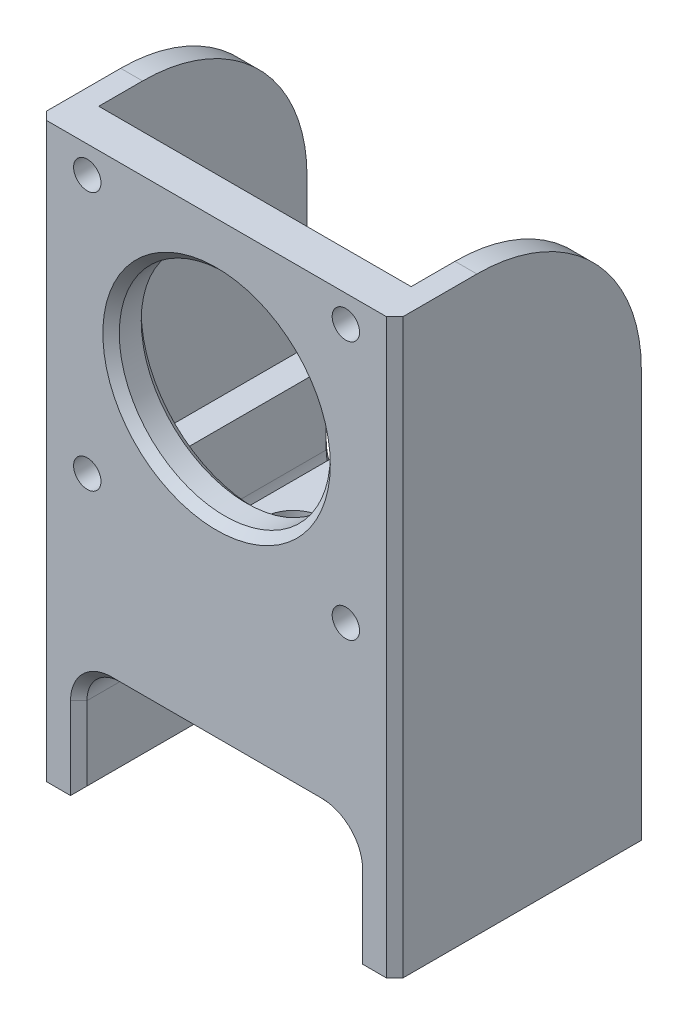
SolidWorks part; units mm, degrees
material "PET"
ref_plane "Front Plane" through (0, 0, 0) normal (0, 0, 1) x (1, 0, 0)
ref_plane "Top Plane" through (0, 0, 0) normal (0, 1, 0) x (1, 0, 0)
ref_plane "Right Plane" through (0, 0, 0) normal (1, 0, 0) x (0, 0, -1)
sketch "Sketch1" plane through (0, 0, 0) normal (0, 0, 1) x (1, 0, 0)
  line L0 (32.5, 28.5) -> (-32.5, 28.5)
  line L1 (-32.5, 28.5) -> (-32.5, -76)
  line L2 (-32.5, -76) -> (-25.15, -76)
  line L3 (-25.15, -76) -> (-25.15, -55)
  line L4 (-25.15, -55) -> (25.15, -55)
  line L5 (0, 28.5) -> (0, -55) construction
  line L6 (-33.5668, 0) -> (21.693, 0) construction
  line L7 (32.5, -76) -> (25.15, -76)
  line L8 (25.15, -76) -> (25.15, -55)
  line L9 (32.5, 28.5) -> (32.5, -76)
  circle A0 centre (0, 0) radius 19.25
  dimension "D1" = 38.5
  dimension "D2" = 65
  dimension "D3" = 28.5
  dimension "D4" = 76
  dimension "D5" = 50.3
  dimension "D6" = 55
extrude "Boss-Extrude1" add sketch "Sketch1" along normal mid plane 45
sketch "Sketch2" plane through (0, 0, -22.5) normal (0, 0, -1) x (-1, 0, 0)
  line L0 (-8.62, -49) -> (-23.5, -49)
  line L1 (-23.5, -28.5) -> (-8.62, -28.5) construction
  line L2 (-32.5, 28.5) -> (32.5, 28.5) construction
  line L3 (28.5, 28.5) -> (-28.5, 28.5)
  line L4 (-28.5, -28.5) -> (-28.5, 28.5)
  line L6 (25.15, -55) -> (-25.15, -55) construction
  line L7 (0, 64.9448) -> (0, 15.4596) construction
  line L8 (-8.62, -49) -> (-8.62, -28.5)
  line L9 (-8.62, -28.5) -> (8.62, -28.5)
  line L10 (-47.1134, 0) -> (-15.0079, 0) construction
  line L11 (8.62, -49) -> (23.5, -49)
  line L12 (8.62, -49) -> (8.62, -28.5)
  line L13 (-28.5, -28.5) -> (-23.5, -28.5)
  line L14 (-23.5, -49) -> (-23.5, -28.5)
  line L15 (23.5, -49) -> (23.5, -28.5)
  line L16 (28.5, -28.5) -> (23.5, -28.5)
  line L17 (28.5, -28.5) -> (28.5, 28.5)
  point P0 (0, 0)
  point P21 (0, -28.5)
  point P24 (0, 28.5)
  dimension "D1" = 28.5
  dimension "D2" = 5
  dimension "D3" = 6
  dimension "D4" = 17.24
  dimension "D5" = 28.5
  dimension "D6" = 14.88
extrude "Cut-Extrude1" cut sketch "Sketch2" against normal blind 38
sketch "Sketch3" plane through (0, 0, 22.5) normal (0, 0, 1) x (1, 0, 0)
  line L1 (23.59, -23.59) -> (-23.59, -23.59) construction
  line L2 (23.59, -23.59) -> (23.59, 23.59) construction
  line L3 (23.59, 23.59) -> (-23.59, 23.59) construction
  line L4 (-23.59, -23.59) -> (-23.59, 23.59) construction
  line L5 (23.59, -23.59) -> (-23.59, 23.59) construction
  line L6 (23.59, 23.59) -> (-23.59, -23.59) construction
  circle A0 centre (-23.59, 23.59) radius 2.5
  circle A1 centre (23.59, 23.59) radius 2.5
  circle A2 centre (23.59, -23.59) radius 2.5
  circle A3 centre (-23.59, -23.59) radius 2.5
  point P0 (0, 0)
  dimension "D2" = 5
  dimension "D1" = 47.18
extrude "Cut-Extrude2" cut sketch "Sketch3" against normal through all
sketch "Sketch4" plane through (0, -28.5, 0) normal (0, 1, 0) x (1, 0, 0)
  line L0 (0, 14) -> (0, -8.5) construction
  line L1 (32.5, -22.5) -> (-32.5, -22.5) construction
  circle A0 centre (0, 14) radius 3.05
  circle A1 centre (0, -8.5) radius 3.05
  dimension "D1" = 6.1
  dimension "D2" = 14
  dimension "D3" = 22.5
extrude "Cut-Extrude3" cut sketch "Sketch4" against normal through all
sketch "Sketch5" plane through (0, -28.5, 0) normal (0, 1, 0) x (1, 0, 0)
  circle A0 centre (0, 14) radius 5.5
  circle A1 centre (0, -8.5) radius 5.5
  dimension "D1" = 11
extrude "Cut-Extrude4" cut sketch "Sketch5" against normal blind 7
fillet "Fillet1" radius 6 2 edges at (-25.15, -55, 0) (25.15, -55, 0)
fillet "Fillet2" 2 edges at (23.5, -49, -3.5) (8.62, -49, -3.5) type full round first side face at (23.5, -38.75, -3.5) second side face at (8.62, -38.75, -3.5) middle face at (16.06, -49, -3.5)
fillet "Fillet3" 2 edges at (-8.62, -49, -3.5) (-23.5, -49, -3.5) type full round first side face at (-8.62, -38.75, -3.5) second side face at (-23.5, -38.75, -3.5) middle face at (-16.06, -49, -3.5)
fillet "Fillet4" radius 7.44 6 edges at (-8.62, -35.03, 15.5) (-16.06, -49, 15.5) (23.5, -35.03, 15.5) (16.06, -49, 15.5) (-23.5, -35.03, 15.5) (8.62, -35.03, 15.5)
fillet "Fillet5" radius 30 2 edges at (30.5, 28.5, -22.5) (-30.5, 28.5, -22.5)
chamfer "Chamfer1" distance 1.5 angle 45 22 edges at (19.25, 0, 22.5) (-19.25, 0, 15.5) (25.15, -68.5, -22.5) (23.3926, -56.7574, -22.5) (0, -55, -22.5) (-25.15, -68.5, -22.5) (-23.3926, -56.7574, -22.5) (25.15, -68.5, 22.5) (23.3926, -56.7574, 22.5) (-25.15, -68.5, 22.5) (0, -55, 22.5) (-23.3926, -56.7574, 22.5) (23.5, -35.03, -22.5) (16.06, -49, -22.5) (8.62, -35.03, -22.5) (-8.62, -35.03, -22.5) (-16.06, -49, -22.5) (-23.5, -35.03, -22.5) (-32.5, -23.75, 22.5) (32.5, -23.75, 22.5) (-25.15, -76, 0) (25.15, -76, 0)
